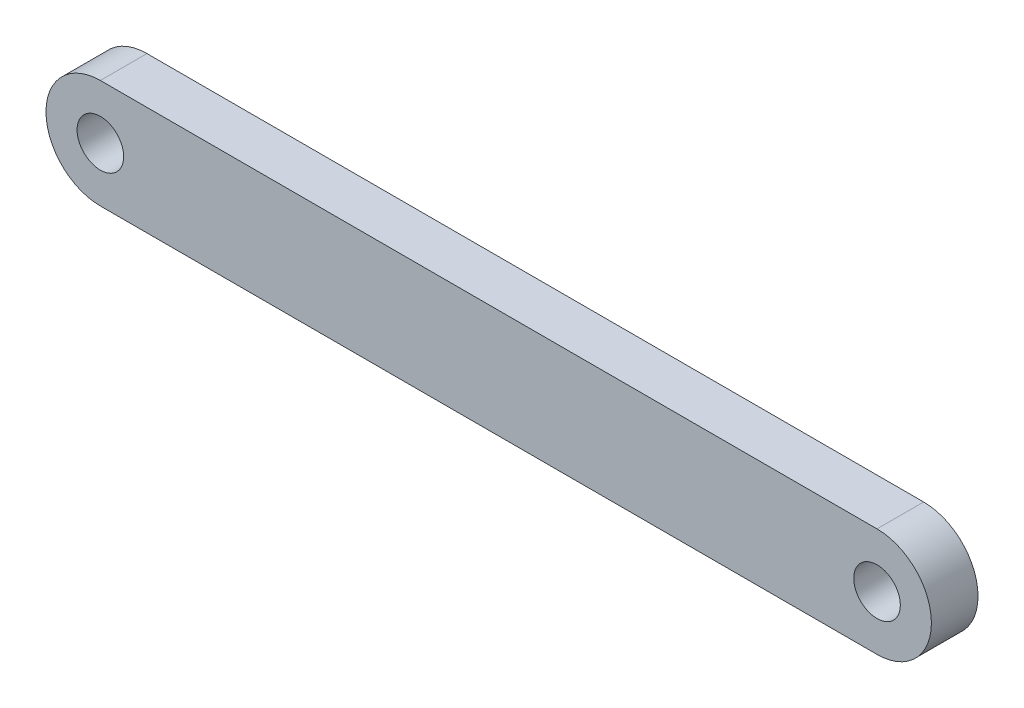
SolidWorks part; units mm, degrees
ref_plane "Front Plane" through (0, 0, 0) normal (0, 0, 1) x (1, 0, 0)
ref_plane "Top Plane" through (0, 0, 0) normal (0, 1, 0) x (1, 0, 0)
ref_plane "Right Plane" through (0, 0, 0) normal (1, 0, 0) x (0, 0, -1)
sketch "Sketch1" plane through (0, 0, 0) normal (0, 0, 1) x (1, 0, 0)
  line L0 (50.75, 28.5) -> (0.75, 28.5)
  line L1 (50.75, 35.5) -> (0.75, 35.5)
  line L2 (0.75, 35.5) -> (0.75, 28.5) construction
  circle A1 centre (50.75, 32) radius 1.5
  arc A2 (50.75, 35.5) -> (50.75, 28.5) centre (50.75, 32) cw
  circle A3 centre (0.75, 32) radius 1.5
  arc A4 (0.75, 28.5) -> (0.75, 35.5) centre (0.75, 32) cw
  point P6 (0, 0)
  point P7 (28.2882, 29.252)
  dimension "D1" = 2
  dimension "D2" = 50
extrude "Boss-Extrude1" add sketch "Sketch1" along normal blind 3
